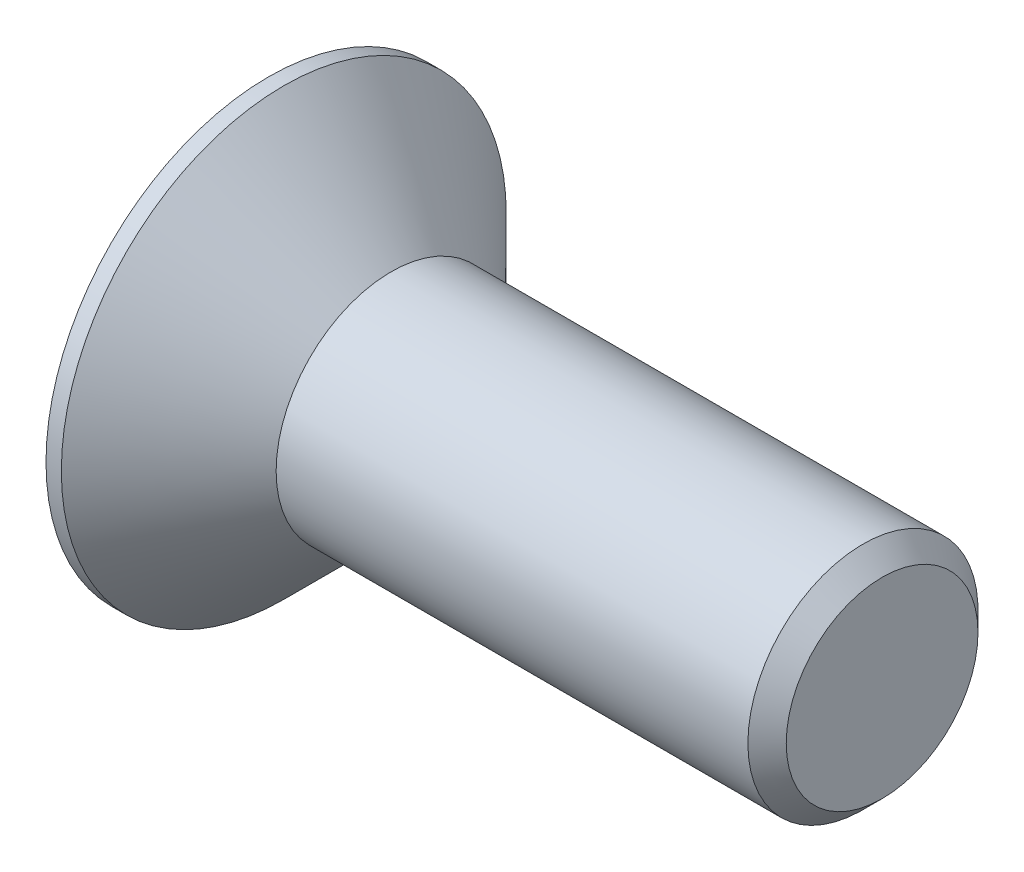
SolidWorks part; units mm, degrees
ref_plane "Front Plane" through (0, 0, 0) normal (0, 0, 1) x (1, 0, 0)
ref_plane "Top Plane" through (0, 0, 0) normal (0, 1, 0) x (1, 0, 0)
ref_plane "Right Plane" through (0, 0, 0) normal (1, 0, 0) x (0, 0, -1)
sketch "Sketch2" plane through (0, 0, 0) normal (0, 0, 1) x (1, 0, 0)
  line L0 (0, 0) -> (0, 2.9)
  line L1 (0, 2.9) -> (0.2, 2.9)
  line L2 (0.2, 2.9) -> (1.6, 1.5)
  line L3 (1.6, 1.5) -> (7.75, 1.5)
  line L4 (7.75, 1.5) -> (8, 1.25)
  line L5 (8, 1.25) -> (8, 0)
  line L6 (8, 0) -> (0, 0)
  line L7 (-2.2818, 0) -> (8.0811, 0) construction
  dimension "D1" = 5.8
  dimension "D2" = 0.2
  dimension "D3" = 45
  dimension "D4" = 8
  dimension "D5" = 0.25
  dimension "D6" = 3
revolve "Revolve1" add sketch "Sketch2" angle 360 about L7
sketch "Sketch3" plane through (0, 0, 0) normal (-1, 0, 0) x (0, 0, 1)
  line L1 (0.7217, -1.25) -> (1.4434, 0)
  line L2 (1.4434, 0) -> (0.7217, 1.25)
  line L3 (0.7217, 1.25) -> (-0.7217, 1.25)
  line L4 (-0.7217, 1.25) -> (-1.4434, 0)
  line L5 (-1.4434, 0) -> (-0.7217, -1.25)
  line L6 (-0.7217, -1.25) -> (0.7217, -1.25)
  circle A0 centre (0, 0) radius 1.25 construction
  dimension "D1" = 2.5
extrude "Cut-Extrude1" cut sketch "Sketch3" against normal blind 0.8
